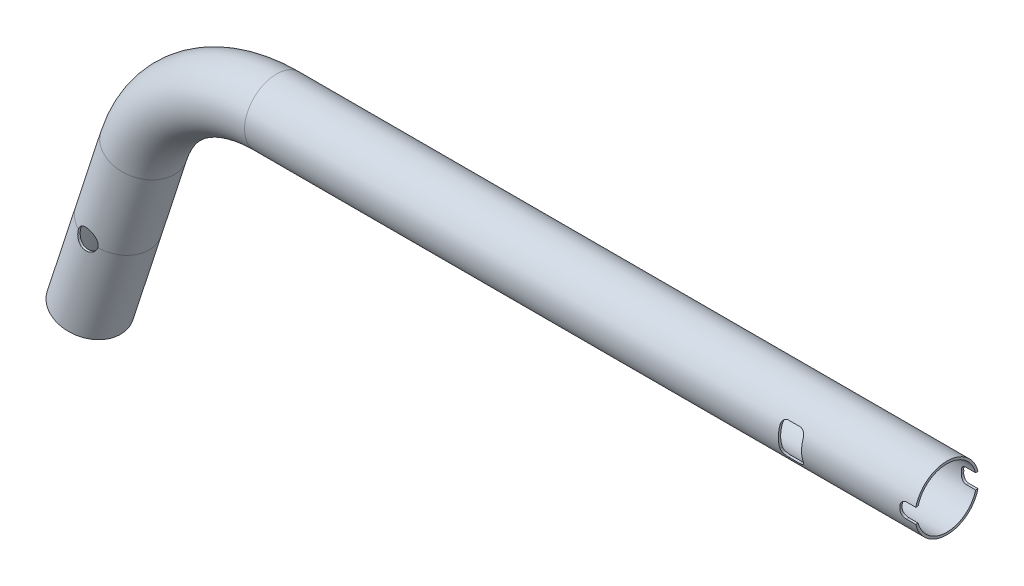
SolidWorks part; units mm, degrees
ref_plane "Front Plane" through (0, 0, 0) normal (0, 0, 1) x (1, 0, 0)
ref_plane "Top Plane" through (0, 0, 0) normal (0, 1, 0) x (1, 0, 0)
ref_plane "Right Plane" through (0, 0, 0) normal (1, 0, 0) x (0, 0, -1)
sketch "Sketch1" plane through (0, 0, 0) normal (0, 0, 1) x (1, 0, 0)
  line L0 (-93.8154, 0) -> (93.8154, 0)
  line L1 (-139.4661, -33.1672) -> (-148.1846, -60)
  line L2 (93.8154, 0) -> (136.8154, 0)
  line L3 (-148.1846, -60) -> (-157.9322, -90)
  arc A0 (-93.8154, 0) -> (-139.4661, -33.1672) centre (-93.8154, -48) ccw
  point P4 (0, 0)
  point P10 (-148.1846, -60)
  dimension "D2" = 48
  dimension "D7" = 90
  dimension "D1" = 72
  dimension "D3" = 60
  dimension "D4" = 242
  dimension "D5" = 43
  dimension "D6" = 72
ref_plane "Plane1" through (93.8154, 0, 0) normal (1, 0, 0) x (0, 0, -1)
sketch "Sketch3" plane through (93.8154, 0, 0) normal (1, 0, 0) x (0, 0, -1)
  circle A0 centre (0, 0) radius 11
  circle A1 centre (0, 0) radius 10.2
  dimension "D1" = 0.8
  dimension "D2" = 22
sweep "Sweep2" add profiles "Sketch3" path "Sketch1"
ref_axis "Axis1" through (136.8154, 0, 0) along (-1, 0, 0)
ref_axis "Axis2" through (-137.4681, -27.018, 0) along (-0.309, -0.9511, 0)
sketch "Sketch4" plane through (0, 0, 0) normal (0, 0, 1) x (1, 0, 0)
  line L0 (-158.6462, -56.6008) -> (-137.723, -63.3992) construction
  line L1 (93.8154, -101.4635) -> (93.8154, 101.4635) construction
  line L2 (136.8154, 0) -> (93.8154, 0) construction
  line L3 (136.8154, -11) -> (136.8154, 11) construction
  line L4 (136.8154, 0) -> (-93.8154, 0) construction
  line L6 (91.8154, -5.5) -> (95.8154, -5.5)
  line L7 (89.8154, -3.5) -> (89.8154, 3.5)
  line L8 (91.8154, 5.5) -> (95.8154, 5.5)
  line L9 (97.8154, -3.5) -> (97.8154, 3.5)
  line L10 (89.8154, -5.5) -> (97.8154, 5.5) construction
  line L11 (89.8154, 5.5) -> (97.8154, -5.5) construction
  circle A0 centre (-148.1846, -60) radius 3.5
  arc A1 (91.8154, -5.5) -> (89.8154, -3.5) centre (91.8154, -3.5) cw
  arc A2 (97.8154, -3.5) -> (95.8154, -5.5) centre (95.8154, -3.5) cw
  arc A3 (95.8154, 5.5) -> (97.8154, 3.5) centre (95.8154, 3.5) cw
  arc A4 (91.8154, 5.5) -> (89.8154, 3.5) centre (91.8154, 3.5) ccw
  dimension "D1" = 43
  dimension "D4" = 2
  dimension "D6" = 7
  dimension "D2" = 8
  dimension "D3" = 11
extrude "Cut-Extrude1" cut sketch "Sketch4" along normal up to next
sketch "Sketch5" plane through (0, 0, 0) normal (0, 0, 1) x (1, 0, 0)
  line L0 (-157.8854, -56.848) -> (-138.4838, -63.152) construction
  circle A0 centre (-148.1846, -60) radius 3.3
extrude "Cut-Extrude2" cut sketch "Sketch5" against normal through all
sketch "Sketch6" plane through (0, 0, 0) normal (0, 0, 1) x (1, 0, 0)
  line L4 (136.8892, 2.5547) -> (136.8154, -2.5547)
  line L5 (136.8154, -11) -> (136.8154, 11) construction
  line L6 (136.8154, -2.5547) -> (133.6154, -2.5547)
  line L7 (131.6154, -0.5547) -> (131.6154, 0.5547)
  line L8 (133.6154, 2.5547) -> (136.8892, 2.5547)
  arc A2 (133.6154, -2.5547) -> (131.6154, -0.5547) centre (133.6154, -0.5547) cw
  arc A3 (133.6154, 2.5547) -> (131.6154, 0.5547) centre (133.6154, 0.5547) ccw
  point P7 (136.8523, 0)
  point P11 (131.6154, -2.5547)
  dimension "D1" = 5.11
  dimension "D3" = 2
  dimension "D2" = 5.2
extrude "Cut-Extrude3" cut sketch "Sketch6" against normal through all and the other way through all
